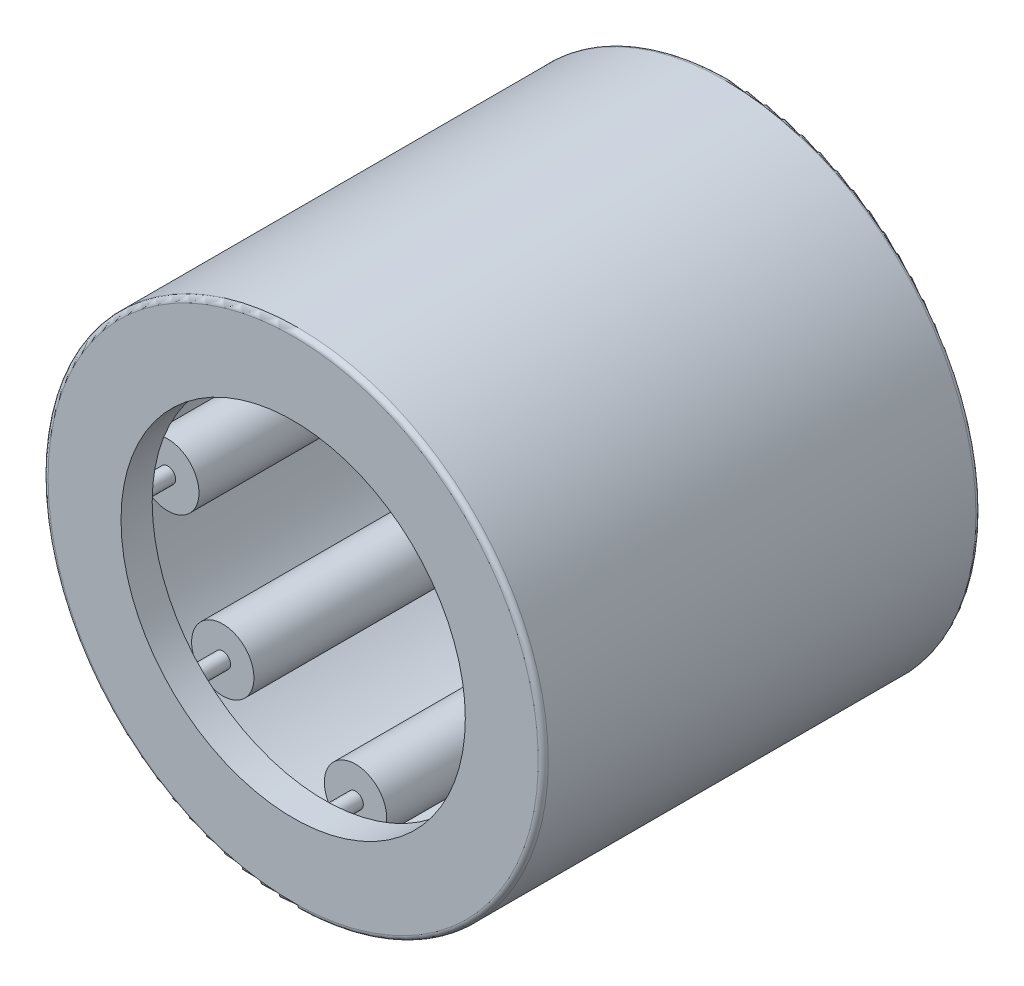
SolidWorks part; units mm, degrees
ref_plane "Front Plane" through (0, 0, 0) normal (0, 0, 1) x (1, 0, 0)
ref_plane "Top Plane" through (0, 0, 0) normal (0, 1, 0) x (1, 0, 0)
ref_plane "Right Plane" through (0, 0, 0) normal (1, 0, 0) x (0, 0, -1)
sketch "Sketch1" plane through (0, 0, 0) normal (1, 0, 0) x (0, 0, -1)
  line L0 (-5.5563, 0) -> (5.5562, 0) construction
  line L1 (0, 0) -> (0, 6.35) construction
  line L2 (-5.5563, 0) -> (-5.5563, 6.35) construction
  line L3 (-5.5563, 6.35) -> (5.5563, 6.35)
  line L4 (5.5563, 6.35) -> (5.5562, 0) construction
  line L5 (5.5562, 0) -> (4.7646, 0) construction
  line L6 (4.7646, 0) -> (4.7646, 5.5584) construction
  line L7 (4.7646, 5.5584) -> (-4.7646, 5.5584)
  line L8 (-4.7646, 5.5584) -> (-4.7646, 0) construction
  line L9 (-4.7646, 0) -> (-5.5563, 0) construction
  line L10 (-5.5563, 6.35) -> (-5.5563, 4.3709)
  line L11 (-5.5563, 4.3709) -> (-4.7646, 4.3709)
  line L12 (-4.7646, 4.3709) -> (-4.7646, 5.5584)
  line L13 (4.7646, 6.35) -> (4.7646, 5.5584) construction
  line L14 (4.7646, 5.5584) -> (4.7646, 4.3709)
  line L15 (4.7646, 4.3709) -> (5.5563, 4.3709)
  line L16 (5.5563, 4.3709) -> (5.5563, 6.35)
  line L17 (4.7646, 5.5584) -> (4.7646, 4.7667) construction
  line L18 (4.7646, 4.7667) -> (4.7646, 3.9751) construction
  point P5 (0, 3.9751)
  dimension "Width" = 11.1125
  dimension "OD" = 12.7
  dimension "Shaft Dia" = 7.9502
revolve "Revolve1" add sketch "Sketch1" angle 360 about L0
sketch "Sketch2" plane through (0, 0, 0) normal (1, 0, 0) x (0, 0, -1)
  line L0 (4.7646, 5.5584) -> (-4.7646, 5.5584) construction
  line L1 (-3.973, 4.7667) -> (3.973, 4.7667) construction
  line L2 (-3.973, 4.7667) -> (-3.973, 5.5584) construction
  line L3 (-3.973, 5.5584) -> (3.973, 5.5584)
  line L4 (3.973, 4.7667) -> (3.973, 5.5584) construction
  line L5 (4.7646, 4.3709) -> (5.5563, 4.3709) construction
  line L6 (-4.7646, 4.7667) -> (-3.973, 4.7667) construction
  line L7 (3.973, 4.7667) -> (4.7646, 4.7667) construction
  line L8 (-5.5563, 4.3709) -> (-4.7646, 4.3709) construction
  line L9 (-3.973, 4.9646) -> (-3.973, 4.5688) construction
  line L10 (-4.7646, 4.7667) -> (-4.7646, 4.3709) construction
  line L11 (-3.973, 5.5584) -> (-3.973, 4.9646)
  line L12 (3.973, 5.5584) -> (3.973, 4.9646)
  line L13 (3.973, 4.9646) -> (-3.973, 4.9646)
  line L14 (0, 5.5584) -> (0, 3.9751) construction
  line L15 (-4.7646, 4.3709) -> (-4.7646, 5.5584) construction
  line L16 (-3.973, 4.5688) -> (-4.7646, 4.5688) construction
  line L17 (0, 0) -> (5.5563, 0) construction
  line L31 (5.5563, -6.35) -> (5.5563, 6.35) construction
  point P16 (0, 4.7667)
revolve "Revolve2" add sketch "Sketch2" angle 360 about L1
sketch "Sketch3" plane through (0, 0, 0) normal (1, 0, 0) x (0, 0, -1)
  line L0 (4.7646, 5.5584) -> (4.7646, 4.3709) construction
  line L1 (-4.7646, 4.7667) -> (4.7646, 4.7667)
  line L2 (-4.7646, 4.7667) -> (-4.7646, 4.9646)
  line L3 (-4.7646, 4.9646) -> (4.7646, 4.9646)
  line L4 (4.7646, 4.7667) -> (4.7646, 4.9646)
  line L5 (0, 0) -> (5.5563, 0) construction
  line L6 (5.5563, -6.35) -> (5.5563, 6.35) construction
revolve "Revolve3" add sketch "Sketch3" angle 360 about L1
ref_axis "Axis1" through (0, 0, -5.5562) along (0, 0, 1)
pattern_circular "CirPattern1" count 8 every 45 about axis through (0, 0, -5.5562) along (0, 0, 1) of bodies 166 167
fillet "Fillet1" radius 0.127 2 edges at (6.35, 0, -5.5563) (6.35, 0, 5.5563)
sketch "Sketch4" plane through (0, 0, 0) normal (1, 0, 0) x (0, 0, -1)
  line L1 (5.4292, 3.9751) -> (3.973, 3.9751)
  line L2 (5.4292, 3.9751) -> (5.4292, 4.3709)
  line L3 (5.4292, 4.3709) -> (3.973, 4.3709)
  line L4 (3.973, 3.9751) -> (3.973, 4.3709)
  line L5 (-5.5563, 4.3709) -> (-4.7646, 4.3709) construction
  line L6 (5.4292, -6.35) -> (5.4292, 6.35) construction
  line L7 (3.973, 5.5584) -> (3.973, 4.9646) construction
revolve "Revolve4" [suppressed] add sketch "Sketch4" angle 360 about L0
sketch "Sketch5" plane through (0, 0, 0) normal (1, 0, 0) x (0, 0, -1)
  line L0 (-5.4292, 6.35) -> (-5.4292, -6.35) construction
  line L1 (-3.973, 3.9751) -> (-5.4292, 3.9751)
  line L2 (-3.973, 3.9751) -> (-3.973, 4.3709)
  line L3 (-3.973, 4.3709) -> (-5.4292, 4.3709)
  line L4 (-5.4292, 3.9751) -> (-5.4292, 4.3709)
  line L6 (-3.973, 5.5584) -> (-3.973, 4.9646) construction
  line L7 (-5.5563, 4.3709) -> (-4.7646, 4.3709) construction
revolve "Revolve5" [suppressed] add sketch "Sketch5" angle 360 about L0
sketch "Front View" plane through (0, 0, 0) normal (0, 0, 1) x (1, 0, 0)
  circle A0 centre (0, 0) radius 3.9751 construction
  circle A1 centre (0, 0) radius 6.35 construction
  dimension "OD" = 12.7
  dimension "ID" = 7.9502
sketch "Right View" plane through (0, 0, 0) normal (1, 0, 0) x (0, 0, -1)
  line L0 (-5.5562, 6.35) -> (5.5562, 6.35) construction
  dimension "Width" = 11.1125
ref_axis "Center Axis 1" through (0, 0, -5.4292) along (0, 0, 1)
ref_plane "Contact Plane 1" through (0, 0, 5.5563) normal (0, 0, 1) x (1, 0, 0)
ref_plane "Contact Plane 2" through (0, 0, -5.5563) normal (0, 0, -1) x (-1, 0, 0)
equation "\"Rollers@CirPattern1\" = \"OD@Sketch1\"*16"
equation "\"D1@Fillet1\" = \"OD@Sketch1\"*.01"
equation "\"Angle@CirPattern1\"= 360 / \"Rollers@CirPattern1\""
equation "\"OD@Front View\"=\"OD@Sketch1\""
equation "\"ID@Front View\"=\"Shaft Dia@Sketch1\""
equation "\"Width@Right View\"=\"Width@Sketch1\""
